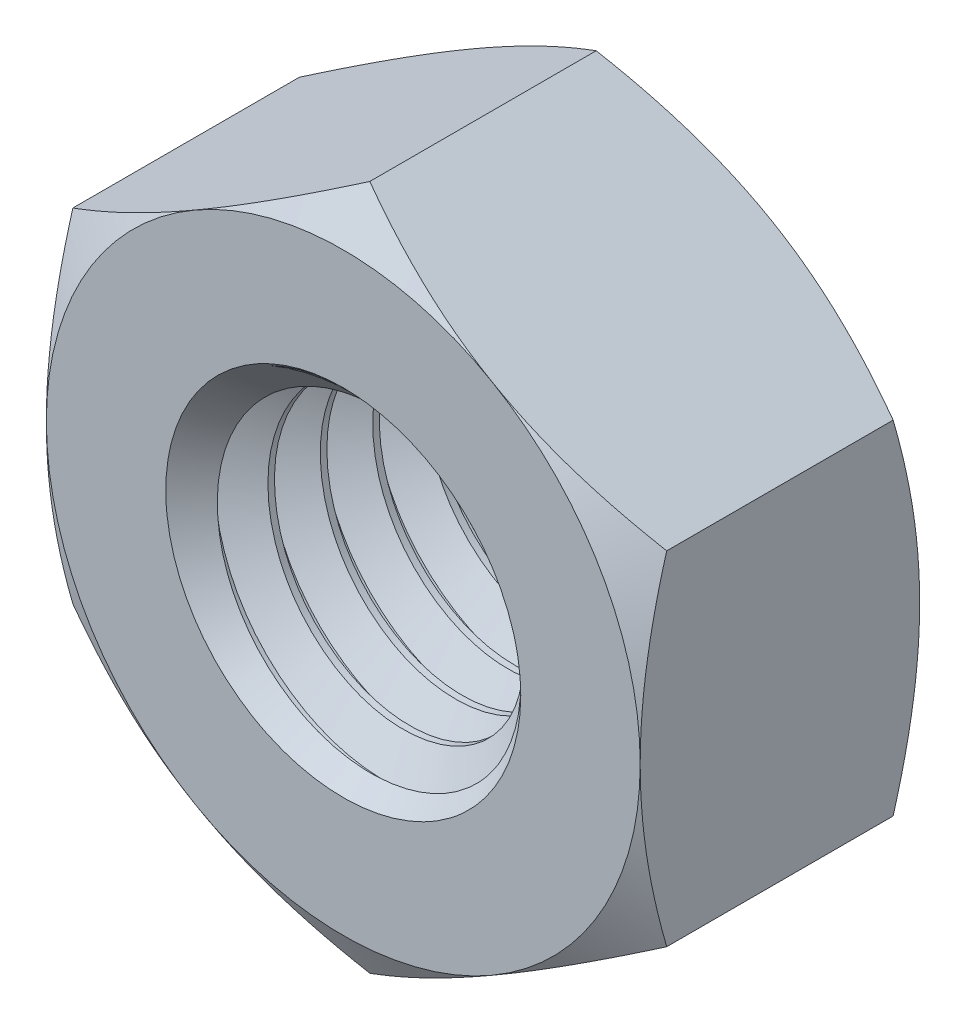
SolidWorks part; units mm, degrees
ref_plane "Front Plane" through (0, 0, 0) normal (0, 0, 1) x (1, 0, 0)
ref_plane "Top Plane" through (0, 0, 0) normal (0, 1, 0) x (1, 0, 0)
ref_plane "Right Plane" through (0, 0, 0) normal (1, 0, 0) x (0, 0, -1)
sketch "Sketch1" plane through (0, 0, 0) normal (1, 0, 0) x (0, 0, -1)
  line L0 (-4, 0) -> (4, 0) construction
  line L1 (-4, -8.5) -> (-4, 8.5) construction
  line L2 (4, -8.5) -> (4, 8.5) construction
  line L3 (-4, -5) -> (-4, 5) construction
  line L4 (-5.4063, 5.1624) -> (-4.6563, 3.8633) construction
  line L5 (-4.6563, 3.8633) -> (-3.9063, 5.1624) construction
  line L6 (-3.9063, 5.1624) -> (-5.4063, 5.1624) construction
  line L7 (-5.3594, 5.0812) -> (-3.9531, 5.0812) construction
  line L8 (-5.3125, 5) -> (-4, 5) construction
  line L9 (-4.75, 4.0257) -> (-4.5625, 4.0257) construction
  line L10 (-4.6563, 4.0257) -> (-4.6563, 3.8633) construction
  line L11 (-4.6563, 5.1624) -> (-4.6563, 5) construction
  point P4 (0, 0)
  point P7 (-4, 0)
  point P11 (4, 0)
  point P14 (-4, 0)
  point P26 (-4.6563, 5.0812)
  point P27 (-4, -5)
  dimension "Height" = 8
  dimension "Width" = 17
  dimension "Thread OD" = 10
  dimension "D1" = 60
  dimension "Pitch" = 1.5
  dimension "D2" = 0.1875
sketch "Sketch2" plane through (0, 0, 0) normal (0, 0, 1) x (1, 0, 0)
  line L1 (0, 9.815) -> (-8.5, 4.9075)
  line L2 (-8.5, 4.9075) -> (-8.5, -4.9075)
  line L3 (-8.5, -4.9075) -> (0, -9.815)
  line L4 (0, -9.815) -> (8.5, -4.9075)
  line L5 (8.5, -4.9075) -> (8.5, 4.9075)
  line L6 (8.5, 4.9075) -> (0, 9.815)
  circle A0 centre (0, 0) radius 8.5 construction
  circle A1 centre (0, 0) radius 5
extrude "Boss-Extrude1" add sketch "Sketch2" along normal up to vertex (4 mm away) and the other way up to vertex (4 mm away) up to point (0, -8.5, 4) other way up to point (0, -8.5, -4)
sketch "Sketch3" plane through (0, 0, 4) normal (0, 0, 1) x (1, 0, 0)
  circle A0 centre (0, 0) radius 8.5
extrude "Cut-Extrude1" cut sketch "Sketch3" against normal through all draft 60 flip side to cut
mirror "Mirror1" about plane through (0, 0, 0) normal (0, 0, 1) of "Cut-Extrude1"
ref_axis "Center Axis 1" through (0, 0, -10.9016) along (0, 0, 1)
ref_plane "Contact Plane 1" through (0, 0, 4) normal (0, 0, 1) x (1, 0, 0)
ref_plane "Contact Plane 2" through (0, 0, -4) normal (0, 0, -1) x (-1, 0, 0)
sketch "Sketch4" plane through (0, 0, 0) normal (1, 0, 0) x (0, 0, -1)
  line L1 (-5.3594, 5.0812) -> (-4.75, 4.0257)
  line L2 (-4.75, 4.0257) -> (-4.5625, 4.0257)
  line L3 (-4.5625, 4.0257) -> (-3.9531, 5.0812)
  line L4 (-5.3594, 5.0812) -> (-3.9531, 5.0812) construction
  line L5 (-5.3594, 5.0812) -> (-3.9531, 5.0812)
sketch "Sketch5" plane through (0, 0, 4) normal (0, 0, 1) x (1, 0, 0)
  circle A0 centre (0, 0) radius 5 construction
  circle A1 centre (0, 0) radius 5
curve "Helix/Spiral1" pitch 1.5 height 9.5 radius 5 centre (0, 0, 4) axis (0, 0, -1) start towards (0, 1, 0)
sweep "Sweep1" add profiles "Sketch4" path "Helix/Spiral1"
sketch "Sketch6" plane through (0, 0, 4) normal (0, 0, 1) x (1, 0, 0)
  circle A1 centre (0, 0) radius 5.0812
extrude "Cut-Extrude2" cut sketch "Sketch6" along normal through all and the other way through all draft 45
sketch "Sketch7" plane through (0, 0, -4) normal (0, 0, -1) x (-1, 0, 0)
  circle A1 centre (0, 0) radius 5.0812
  circle A2 centre (0, 0) radius 5.0812
  dimension "D1" = 0
extrude "Cut-Extrude3" cut sketch "Sketch7" along normal through all and the other way through all draft 45
equation "\"D2@Sketch1\"=\"Pitch@Sketch1\"/8"
equation "\"D4@Helix/Spiral1\"=\"Pitch@Sketch1\""
equation "\"D3@Helix/Spiral1\"=\"Height@Sketch1\"+\"Pitch@Sketch1\""
